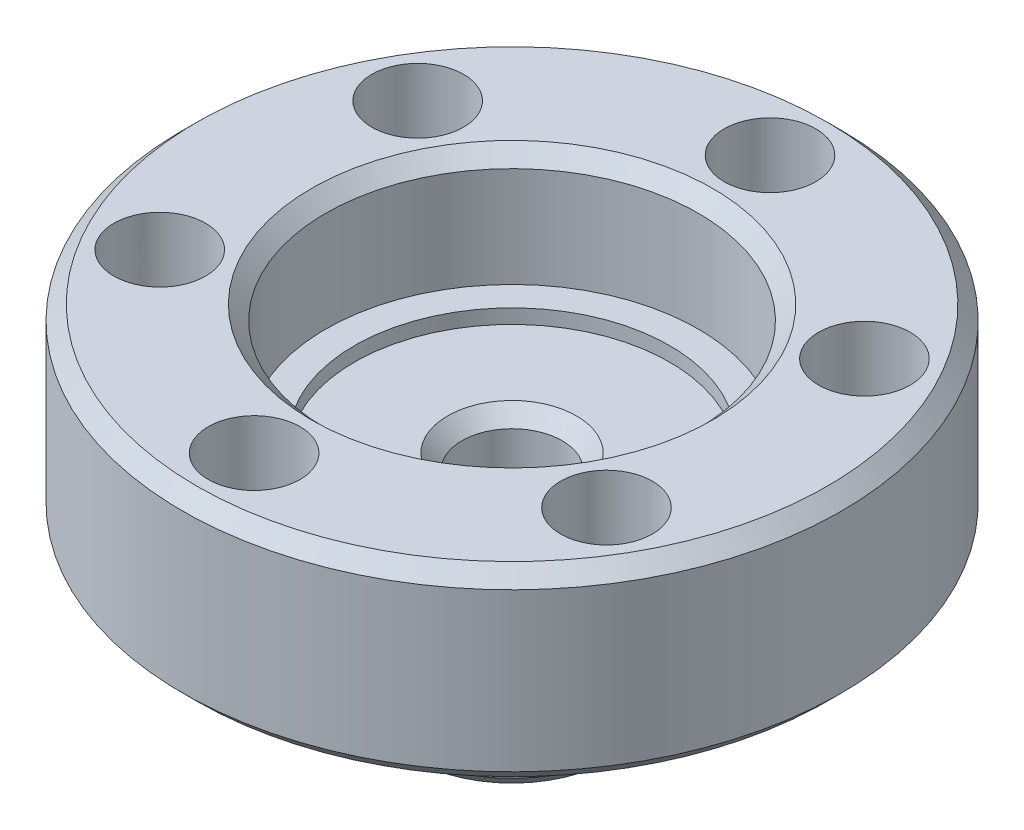
SolidWorks part; units mm, degrees
material "PLA"
ref_plane "Front Plane" through (0, 0, 0) normal (0, 0, 1) x (1, 0, 0)
ref_plane "Top Plane" through (0, 0, 0) normal (0, 1, 0) x (1, 0, 0)
ref_plane "Right Plane" through (0, 0, 0) normal (1, 0, 0) x (0, 0, -1)
sketch "Sketch1" plane through (0, 0, 0) normal (0, 1, 0) x (1, 0, 0)
  circle A0 centre (0, 0) radius 11.5
  dimension "D1" = 23
extrude "Boss-Extrude1" add sketch "Sketch1" along normal blind 6.5
sketch "Sketch2" plane through (0, 0, 0) normal (0, -1, 0) x (1, 0, 0)
  circle A0 centre (0, 0) radius 5
  dimension "D1" = 10
extrude "Boss-Extrude2" add sketch "Sketch2" along normal blind 0.5
sketch "Sketch3" plane through (0, -0.5, 0) normal (0, -1, 0) x (1, 0, 0)
  circle A0 centre (0, 0) radius 4
  dimension "D1" = 8
extrude "Boss-Extrude3" add sketch "Sketch3" along normal blind 5
sketch "Sketch4" plane through (0, 6.5, 0) normal (0, 1, 0) x (1, 0, 0)
  circle A0 centre (0, 0) radius 6.5
  dimension "D1" = 13
extrude "Cut-Extrude1" cut sketch "Sketch4" against normal blind 4
sketch "Sketch5" plane through (0, 2.5, 0) normal (0, 1, 0) x (1, 0, 0)
  circle A0 centre (0, 0) radius 5.5
  dimension "D1" = 11
extrude "Cut-Extrude2" cut sketch "Sketch5" against normal blind 0.5
sketch "Sketch6" plane through (0, 2, 0) normal (0, 1, 0) x (1, 0, 0)
  circle A0 centre (0, 0) radius 1.75
  dimension "D1" = 3.5
extrude "Cut-Extrude3" cut sketch "Sketch6" against normal up to surface (7.5 mm away) up to face at (0, -5.5, -4)
sketch "Sketch7" plane through (0, 6.5, 0) normal (0, 1, 0) x (1, 0, 0)
  line L0 (0, 0) -> (0, 9) construction
  circle A0 centre (0, 9) radius 1.6
  dimension "D2" = 3.2
  dimension "D1" = 9
extrude "Cut-Extrude4" cut sketch "Sketch7" against normal up to surface (6.5 mm away) up to face at (0, 0, -5)
sketch "Sketch8" plane through (0, 0, 0) normal (0, -1, 0) x (1, 0, 0)
  circle A0 centre (0, -9) radius 2
  dimension "D1" = 4
extrude "Cut-Extrude5" cut sketch "Sketch8" against normal blind 4
pattern_circular "CirPattern1" count 6 over 360 about axis through (0, 6.5, 0) along (0, -1, 0) of "Cut-Extrude5", "Cut-Extrude4"
chamfer "Chamfer2" distance 0.5 angle 45 6 edges at (0, 2, 1.75) (0, -5.5, -1.75) (0, -5.5, -4) (0, 0, 11.5) (0, 6.5, 11.5) (0, 6.5, 6.5)
